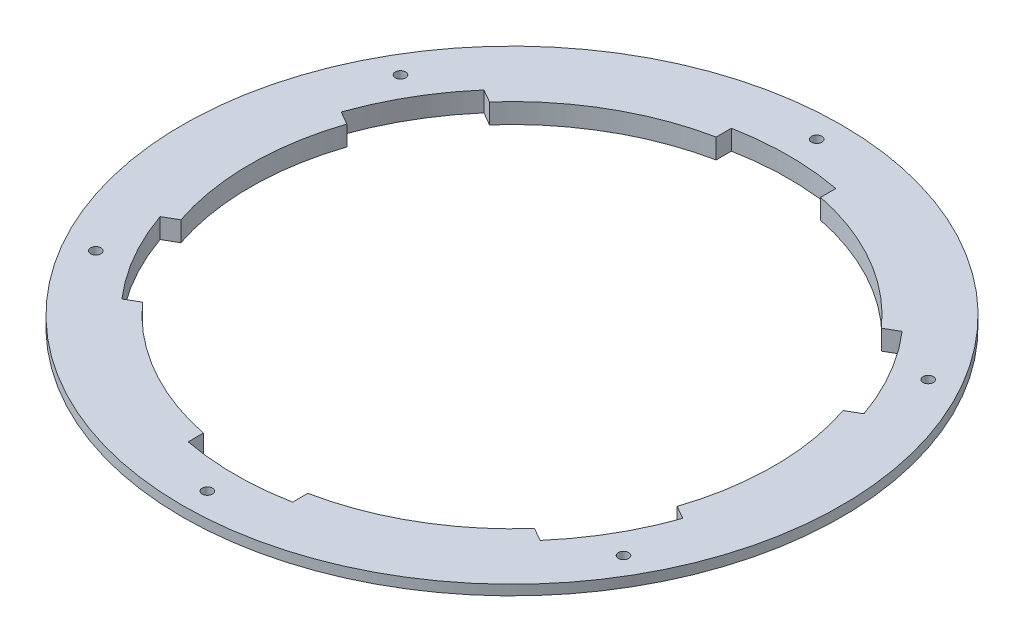
SolidWorks part; units mm, degrees
material "6061 Alloy"
ref_plane "Front Plane" through (0, 0, 0) normal (0, 0, 1) x (1, 0, 0)
ref_plane "Top Plane" through (0, 0, 0) normal (0, 1, 0) x (1, 0, 0)
ref_plane "Right Plane" through (0, 0, 0) normal (1, 0, 0) x (0, 0, -1)
sketch "Sketch1" plane through (0, 0, 0) normal (0, 1, 0) x (1, 0, 0)
  line L0 (-13.335, -65.4575) -> (-13.335, -69.3414)
  line L1 (13.335, -65.4575) -> (13.335, -69.3414)
  circle A0 centre (0, 0) radius 66.802
  circle A1 centre (0, 0) radius 84.1375
  circle A2 centre (0, 0) radius 70.612
  circle A3 centre (0, -77.7875) radius 1.3208
  dimension "D1" = 133.604
  dimension "D2" = 168.275
  dimension "D8" = 2.6416
  dimension "D4" = 13.335
  dimension "D5" = 13.335
  dimension "D7" = 77.7875
  dimension "D3" = 3.81
extrude "Boss-Extrude1" add sketch "Sketch1" along normal blind 5.08 contours L1 A2 L0 A0 | A1 A2 A0 region at (-15.3232, 0, 67.3995) region at (-81.7577, 0, 0)
pattern_circular "CirPattern1" count 6 over 360 about axis through (0, 5.08, 0) along (0, 1, 0) of face at (-13.335, 2.54, 67.3995) of face at (0, 2.54, 69.9767) of face at (13.335, 2.54, 67.3995) of face at (0, 5.08, 79.1083)
sketch "Sketch2" plane through (0, 0, 0) normal (1, 0, 0) x (0, 0, -1)
  line L0 (84.1375, 5.08) -> (-84.1375, 5.08) construction
  line L1 (-84.1375, 0) -> (84.1375, 0) construction
  line L2 (84.1375, 5.08) -> (-84.1375, 5.08)
  line L3 (-84.1375, 0) -> (84.1375, 0)
  line L4 (0, 0) -> (0, 5.08) construction
  circle A0 centre (-83.2231, 0) radius 2.667
  dimension "D1" = 5.334
  dimension "D2" = 0.9144
revolve "Cut-Revolve1" cut sketch "Sketch2" angle 360 about L4 region at (0, 0, 85.8147)
sketch "Sketch4" plane through (0, 0, 0) normal (0, -1, 0) x (1, 0, 0)
  line L0 (0, 0) -> (36.9888, -64.0664) construction
  line L1 (0, 0) -> (0, -39.7137) construction
  circle A0 centre (36.9888, -64.0664) radius 5.588
  circle M34 centre (0, 0) radius 80.5561
  dimension "D2" = 11.176
  dimension "D1" = 73.9775
  dimension "D3" = 30
extrude "Cut-Extrude1" cut sketch "Sketch4" against normal blind 1.905 contours A0 M34 region at (36.9888, 0, -64.0664)
pattern_circular "CirPattern2" count 3 over 360 about axis through (0, 0, 0) along (0, 1, 0) of "Cut-Extrude1"
equation "\"Middle Coupler Inner Daimeter\"= 4.75in"
equation "\"Middle Coupler  Wall Thickness\" = 0.25in"
equation "\"Middle Coupler Bottom Thickness\"= 0.2in"
equation "\"Bearing Rail Offset\"= 0.45in"
equation "\"3-56 UNF Tap\"= 0.089in"
equation "\"3-56 UNF Clearance\"= 0.104in"
equation "\"Ball Bearing Distance\"= 0.03in"
equation "\"D1@Sketch1\"=\"Middle Coupler Inner Daimeter\"+0.5+0.005*2in"
equation "\"TCA Outer Diameter\" = 6.625in"
equation "\"D2@Sketch1\"=\"TCA Outer Diameter\""
equation "\"D4@Sketch1\"=0.50 + (0.05/2)"
equation "\"D5@Sketch1\"=\"D4@Sketch1\""
equation "\"D7@Sketch1\"=(\"D2@Sketch1\"-0.5)/2"
equation "\"D8@Sketch1\"=\"3-56 UNF Clearance\""
equation "\"D2@Sketch2\"=\"Interstage Aeroframe Wall Thickness\"/2"
equation "\"Interstage Aeroframe Wall Thickness\" = 0.072in"
equation "\"D1@Sketch4\"=((\"Middle Coupler Inner Daimeter\"+0.625in)/2in+0.225in)"
equation "\"Compression Spring OD\"= 0.42in"
equation "\"10-24 Tap\"= 0.157in"
equation "\"10-24 Clearance\"= 0.196in"
equation "\"D2@Sketch4\"=\"Compression Spring OD\"+0.02"
equation "\"D3@Sketch1\"=0.125in+(0.05/2)"
equation "\"Lower Stage Fuselage Wall Thickness\" = 0.25in"
equation "\"6-32 Tap\" = 0.107in"
equation "\"1/4-20 Tap\" = 0.201in"
